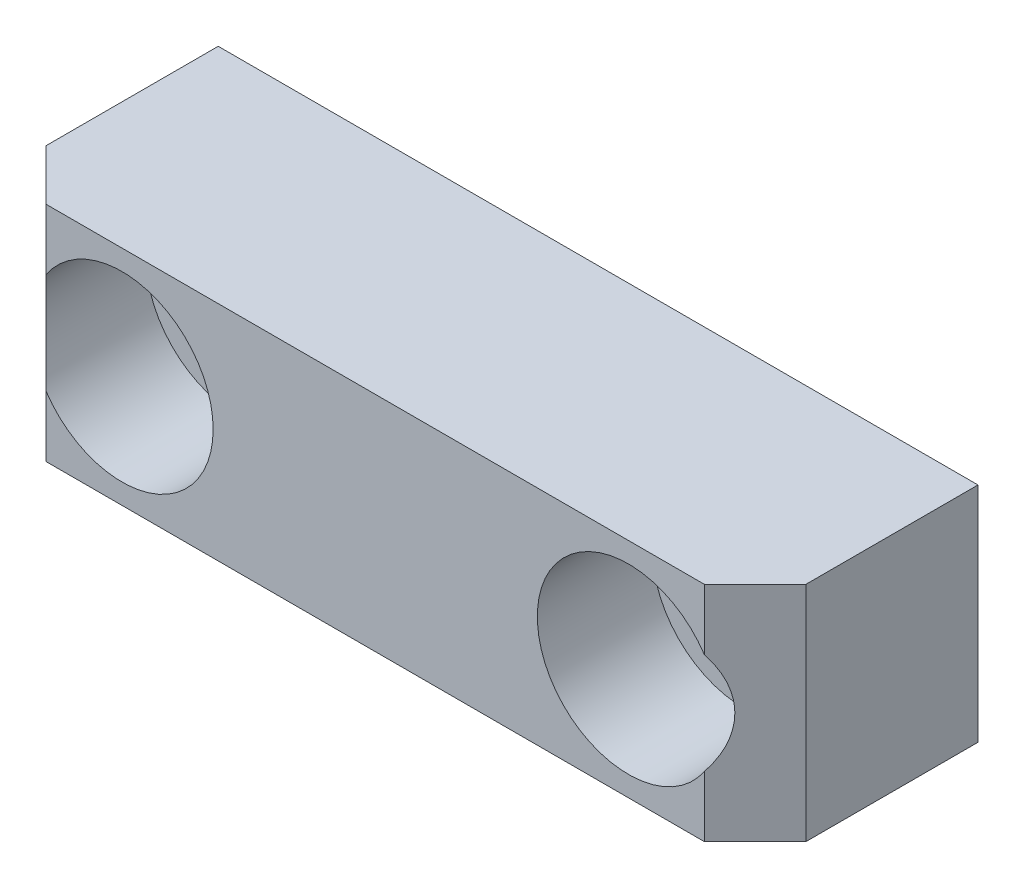
SolidWorks part; units mm, degrees
ref_plane "Front" through (0, 0, 0) normal (0, 0, 1) x (1, 0, 0)
ref_plane "Top" through (0, 0, 0) normal (0, 1, 0) x (1, 0, 0)
ref_plane "Right" through (0, 0, 0) normal (1, 0, 0) x (0, 0, -1)
sketch "Sketch1" plane through (0, 0, 0) normal (0, 1, 0) x (1, 0, 0)
  line L0 (0, -13.5945) -> (0, 30.1479) construction
  line L1 (-37.5, 0) -> (37.5, 0)
  line L2 (-37.5, 0) -> (-37.5, 22)
  line L3 (-37.5, 22) -> (37.5, 22)
  line L4 (37.5, 0) -> (37.5, 22)
  dimension "D1" = 22
  dimension "D2" = 75
extrude "Boss-Extrude1" add sketch "Sketch1" along normal blind 22
hole_wizard "CBORE for M10 Socket Head Cap Screw1" positions "Sketch3" profile "Sketch2" counterbore size "M10" standard "JIS" end condition through all
sketch "Sketch3" plane through (0, 0, 0) normal (0, 0, 1) x (1, 0, 0)
  line L0 (0, -4.2332) -> (0, 26.8552) construction
  line L2 (-37.5, 0) -> (37.5, 0) construction
  point P0 (25, 11)
  point P8 (-25, 11)
  dimension "D1" = 50
  dimension "D2" = 11
sketch "Sketch2" plane through (25, 11, 0) normal (1, 0, 0) x (0, -1, 0)
  line L0 (0, 0) -> (0, 22)
  line L1 (0, 22) -> (6, 22)
  line L3 (6, 22) -> (6, 11.366)
  line L4 (6, 11.366) -> (9, 11.366)
  line L5 (9, 11.366) -> (9, 0)
  line L7 (9, 0) -> (0, 0)
  line L11 (0, -6.35) -> (0, 107.95) construction
  dimension "Thru Hole Dia." = 12
  dimension "Thru Hole Depth" = 22
  dimension "C'Bore Dia." = 18
  dimension "C'Bore Depth" = 11.366
chamfer "Chamfer1" distance 5 angle 45 2 edges at (-37.5, 11, 0) (37.5, 11, 0)
